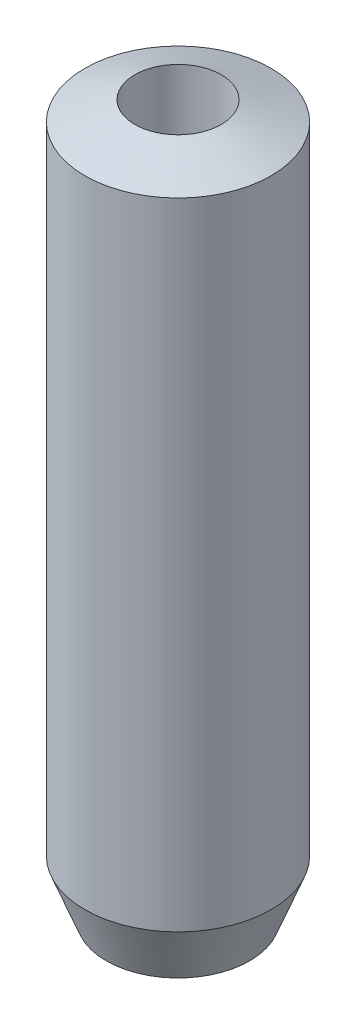
SolidWorks part; units mm, degrees
ref_plane "Front Plane" through (0, 0, 0) normal (0, 0, 1) x (1, 0, 0)
ref_plane "Top Plane" through (0, 0, 0) normal (0, 1, 0) x (1, 0, 0)
ref_plane "Right Plane" through (0, 0, 0) normal (1, 0, 0) x (0, 0, -1)
sketch "Sketch1" plane through (0, 0, 0) normal (0, 1, 0) x (1, 0, 0)
  circle A0 centre (0, 0) radius 7.5
  dimension "SHAFT_OD" = 15
extrude "Boss-Extrude1" add sketch "Sketch1" along normal blind 57.3543
sketch "Sketch2" plane through (0, 0, 0) normal (0, 1, 0) x (1, 0, 0)
  circle A0 centre (0, 0) radius 3.4762
  dimension "BORE_D" = 6.9525
extrude "Cut-Extrude1" cut sketch "Sketch2" along normal through all
chamfer "Chamfer1" distance 1.7227 angle 68.764 2 edges at (0, 57.3543, 7.5) (0, 0, 7.5) first distance on face at (0, 57.3543, 7.5) first distance on face at (0, 0, 3.4762)
